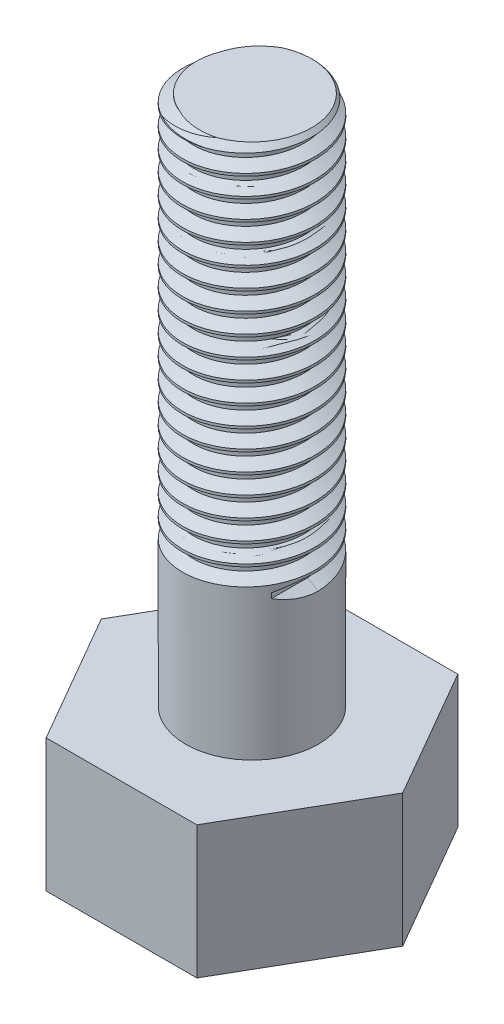
SolidWorks part; units mm, degrees
ref_plane "Front Plane" through (0, 0, 0) normal (0, 0, 1) x (1, 0, 0)
ref_plane "Top Plane" through (0, 0, 0) normal (0, 1, 0) x (1, 0, 0)
ref_plane "Right Plane" through (0, 0, 0) normal (1, 0, 0) x (0, 0, -1)
sketch "Sketch1" plane through (0, 0, 0) normal (0, 1, 0) x (1, 0, 0)
  line L1 (11.3584, 0) -> (5.6792, 9.8367)
  line L2 (5.6792, 9.8367) -> (-5.6792, 9.8367)
  line L3 (-5.6792, 9.8367) -> (-11.3584, 0)
  line L4 (-11.3584, 0) -> (-5.6792, -9.8367)
  line L5 (-5.6792, -9.8367) -> (5.6792, -9.8367)
  line L6 (5.6792, -9.8367) -> (11.3584, 0)
  circle A0 centre (0, 0) radius 9.8367 construction
extrude "Boss-Extrude1" add sketch "Sketch1" along normal blind 10
sketch "Sketch3" plane through (0, 10, 0) normal (0, 1, 0) x (1, 0, 0)
  circle A0 centre (0, 0) radius 5
extrude "Boss-Extrude2" add sketch "Sketch3" along normal blind 40
chamfer "Chamfer4" distance 0.5 angle 45 1 edges at (0, 50, 5)
thread "Thread1" pitch 1.5 method cut profile "Thread Profile1" start angle 0, offset 10, length 0, pitch 1.5, diameter 10
ref_plane "Plane1" through (5, 20, 0) normal (0, 0, 1) x (1, 0, 0)
sketch "Thread Profile1" plane through (5, 20, 0) normal (0, 0, 1) x (1, 0, 0)
  line L0 (0, 0) -> (0, 1.5) construction
  line L11 (0, 0) -> (0, 1.3125)
  line L12 (0, 1.3125) -> (-0.8119, 0.8437)
  line L13 (-0.8119, 0.8437) -> (-0.8119, 0.4687)
  line L15 (-0.8119, 0.4687) -> (0, 0)
  line L17 (-0.8119, 0.6562) -> (0, 0.6562) construction
  point P2 (0, 0)
  dimension "Pitch" = 1.5
  dimension "Profile_Angle" = 60
  dimension "Profile_Land" = 0.375
  dimension "Profile_Height" = 0.8119
sketch "Sketch7" plane through (0, 0, 0) normal (0, 0, -1) x (-1, 0, 0)
  line L4 (-5, 20) -> (-4.1881, 20.4687)
  line L5 (-4.1881, 20.4687) -> (-4.1881, 20.8437)
  line L6 (-4.1881, 20.8437) -> (-5, 21.3125)
  line L7 (-5, 21.3125) -> (-5, 20)
  line L8 (-5, 20) -> (-4.1881, 20.4687)
  line L9 (-4.1881, 20.4687) -> (-4.1881, 20.8437)
  line L10 (-4.1881, 20.8437) -> (-5, 21.3125)
  line L11 (-5, 21.3125) -> (-5, 20)
  dimension "D1" = 0
extrude "Cut-Extrude1" cut sketch "Sketch7" against normal blind 40
